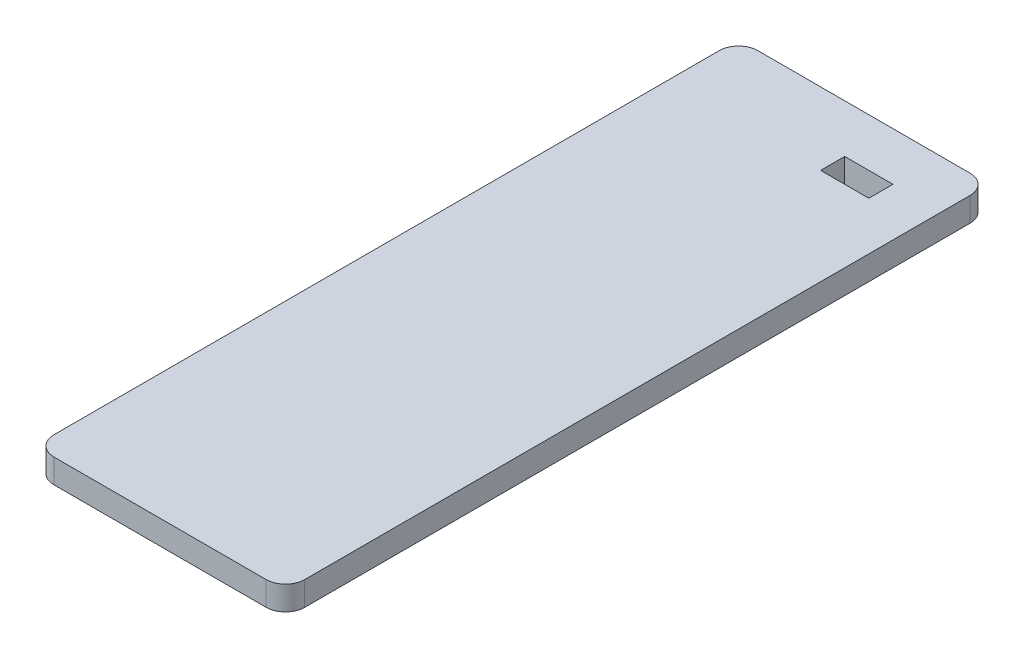
SolidWorks part; units mm, degrees
material "Acrylic (Medium-high impact)"
ref_plane "Front Plane" through (0, 0, 0) normal (0, 0, 1) x (1, 0, 0)
ref_plane "Top Plane" through (0, 0, 0) normal (0, 1, 0) x (1, 0, 0)
ref_plane "Right Plane" through (0, 0, 0) normal (1, 0, 0) x (0, 0, -1)
ref_plane "Plane1" through (0, 0, 0) normal (0, 1, 0) x (1, 0, 0)
sketch "Sketch1" plane through (0, 0, 0) normal (0, 1, 0) x (1, 0, 0)
  line L1 (-26.2811, -36.4838) -> (6.7489, -36.4838)
  line L2 (-26.2811, -36.4838) -> (-26.2811, 56.2162)
  line L3 (-26.2811, 56.2162) -> (6.7489, 56.2162)
  line L4 (6.7489, -36.4838) -> (6.7489, 56.2162)
  dimension "D1" = 92.7
  dimension "D2" = 33.03
extrude "Boss-Extrude1" add sketch "Sketch1" along normal blind 3.175
sketch "Sketch2" plane through (0, 3.175, 0) normal (0, 1, 0) x (1, 0, 0)
  line L1 (-5.9511, 46.6912) -> (0.3989, 46.6912)
  line L2 (-5.9511, 46.6912) -> (-5.9511, 49.8662)
  line L3 (-5.9511, 49.8662) -> (0.3989, 49.8662)
  line L4 (0.3989, 46.6912) -> (0.3989, 49.8662)
  line L6 (6.7489, 56.2162) -> (-26.2811, 56.2162) construction
  line L7 (6.7489, -36.4838) -> (6.7489, 56.2162) construction
  dimension "D1" = 6.35
  dimension "D2" = 3.175
  dimension "D3" = 6.35
  dimension "D4" = 6.35
extrude "Cut-Extrude1" cut sketch "Sketch2" against normal through all
fillet "Fillet1" radius 2.54 4 edges at (-26.2811, 1.5875, -56.2162) (6.7489, 1.5875, -56.2162) (6.7489, 1.5875, 36.4838) (-26.2811, 1.5875, 36.4838)
